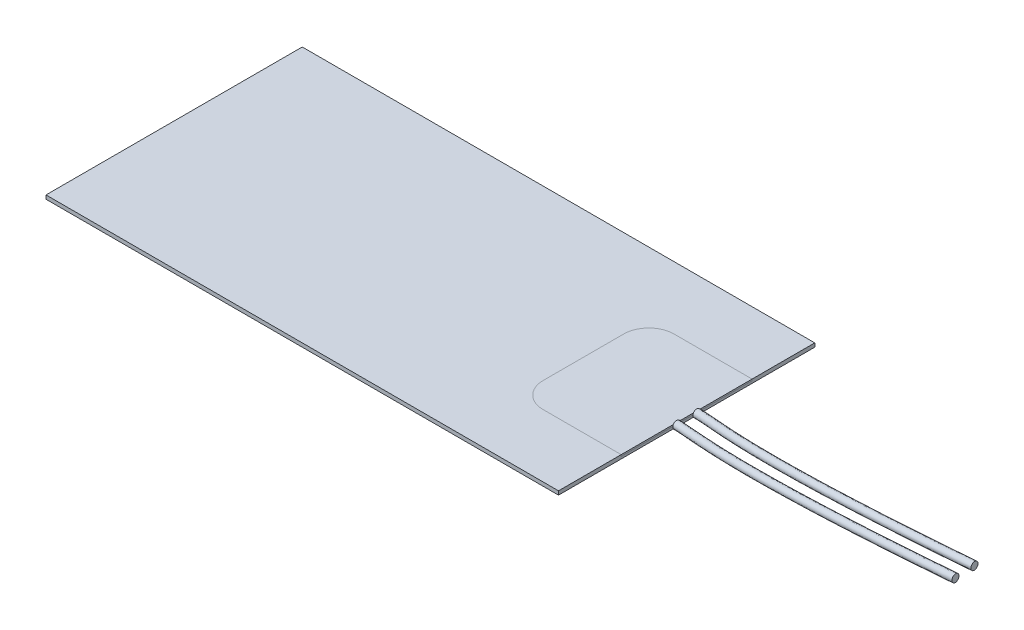
SolidWorks part; units mm, degrees
ref_plane "Front Plane" through (0, 0, 0) normal (0, 0, 1) x (1, 0, 0)
ref_plane "Top Plane" through (0, 0, 0) normal (0, 1, 0) x (1, 0, 0)
ref_plane "Right Plane" through (0, 0, 0) normal (1, 0, 0) x (0, 0, -1)
sketch "Sketch1" plane through (0, 0, 0) normal (0, 1, 0) x (1, 0, 0)
  line L1 (-50.9, 25.45) -> (50.9, 25.45)
  line L2 (-50.9, 25.45) -> (-50.9, -25.45)
  line L3 (-50.9, -25.45) -> (50.9, -25.45)
  line L4 (50.9, 25.45) -> (50.9, -25.45)
  line L5 (-50.9, 25.45) -> (50.9, -25.45) construction
  line L6 (-50.9, -25.45) -> (50.9, 25.45) construction
  point P4 (0, 0)
  point P5 (0, 0)
  dimension "D1" = 101.8
  dimension "D2" = 50.9
extrude "Heater" add sketch "Sketch1" along normal blind 0.75
sketch "Sketch2" plane through (0, 0.75, 0) normal (0, 1, 0) x (1, 0, 0)
  line L0 (50.9, -25.45) -> (50.9, 25.45) construction
  line L1 (35.4, 13) -> (50.9, 13)
  line L2 (30.4, 8) -> (30.4, -8)
  line L3 (35.4, -13) -> (50.9, -13)
  line L4 (50.9, 13) -> (50.9, -13)
  line L5 (30.4, 13) -> (50.9, -13) construction
  line L6 (30.4, -13) -> (50.9, 13) construction
  line L7 (0, 0) -> (40.65, 0) construction
  arc A0 (35.4, -13) -> (30.4, -8) centre (35.4, -8) cw
  arc A1 (30.4, 8) -> (35.4, 13) centre (35.4, 8) cw
  point P4 (40.65, 0)
  dimension "D3" = 5
  dimension "D1" = 26
  dimension "D2" = 20.5
extrude "Cutout" cut sketch "Sketch2" against normal blind 0.3
sketch "Sketch3" plane through (0, 0.45, 0) normal (0, 1, 0) x (1, 0, 0)
  line L0 (50.9, -13) -> (50.9, 13) construction
  line L1 (35.4, -13) -> (50.9, -13) construction
  line L2 (30.4, 8) -> (30.4, -8) construction
  line L3 (50.9, 13) -> (35.4, 13) construction
  line L4 (50.9, -13) -> (50.9, 13)
  line L5 (35.4, -13) -> (50.9, -13)
  line L6 (30.4, 8) -> (30.4, -8)
  line L7 (50.9, 13) -> (35.4, 13)
  arc A0 (30.4, -8) -> (35.4, -13) centre (35.4, -8) ccw construction
  arc A1 (35.4, 13) -> (30.4, 8) centre (35.4, 8) ccw construction
  arc A2 (30.4, -8) -> (35.4, -13) centre (35.4, -8) ccw
  arc A3 (35.4, 13) -> (30.4, 8) centre (35.4, 8) ccw
extrude "Connector" add sketch "Sketch3" along normal blind 0.3 separate body
sketch "Wire Sketch" plane through (50.9, 0, 0) normal (1, 0, 0) x (0, 0, -1)
  line L0 (0, 0.75) -> (0, 0) construction
  line L1 (-13, 0.75) -> (13, 0.75) construction
  line L2 (-25.45, 0) -> (25.45, 0) construction
  line L3 (0, 0.375) -> (-2, 0.375) construction
  circle A0 centre (-2, 0.375) radius 0.75
  circle A1 centre (2, 0.375) radius 0.75
  point P9 (-1.1546, 0.45)
  point P10 (0, 0)
  dimension "D1" = 1.5
  dimension "D2" = 2
ref_plane "Midplane" through (0, 0.375, 0) normal (0, -1, 0) x (-1, 0, 0)
sketch "Sketch5" plane through (0, 0.375, 0) normal (0, -1, 0) x (-1, 0, 0)
  line L0 (-50.9, 2.75) -> (-50.9, 1.25) construction
  line L1 (-50.9, 2) -> (-54.6867, 2.1088) construction
  line L2 (-54.6867, 2.1088) -> (-62.8368, -0.2505) construction
  line L3 (-62.8368, -0.2505) -> (-104.7421, 3.3281) construction
  line L5 (-50.9, 0) -> (-50.9, -2) construction
  line L6 (-50.9, -2) -> (-56.0271, -1.9127) construction
  line L7 (-56.0271, -1.9127) -> (-63.373, -4.4328) construction
  line L8 (-63.373, -4.4328) -> (-103.7292, -0.2505) construction
  spline S0 degree 3 poles (-50.9, 2) (-54.6867, 2.1088) (-62.8368, -0.2505) (-104.7421, 3.3281) knots 0 0 0 0 1 1 1 1
  spline S1 degree 3 poles (-50.9, -2) (-56.0271, -1.9127) (-63.373, -4.4328) (-103.7292, -0.2505) knots 0 0 0 0 1 1 1 1
  point P8 (-56.0271, -1.9127)
  point P10 (0, 0)
  point P14 (-54.6867, 2.1088)
  point P15 (-62.8368, -0.2505)
  point P16 (-63.373, -4.4328)
  point P17 (-104.7421, 3.3281)
  point P18 (-103.7292, -0.2505)
sweep "Sweep1" add profiles "Wire Sketch" path "Sketch5"
